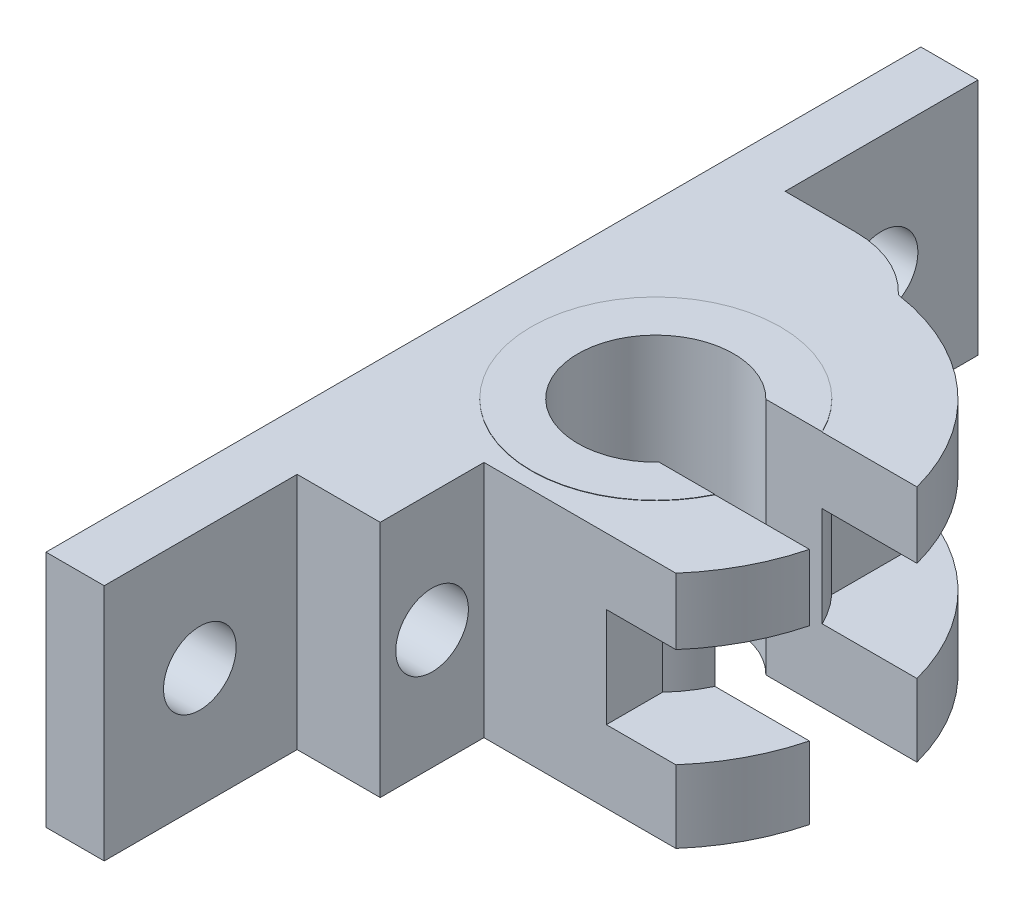
SolidWorks part; units mm, degrees
ref_plane "前基準面" through (0, 0, 0) normal (0, 0, 1) x (1, 0, 0)
ref_plane "上基準面" through (0, 0, 0) normal (0, 1, 0) x (1, 0, 0)
ref_plane "右基準面" through (0, 0, 0) normal (1, 0, 0) x (0, 0, -1)
sketch "草圖1" plane through (0, 0, 0) normal (0, 1, 0) x (1, 0, 0)
  circle A0 centre (0, 0) radius 9.68
  dimension "D1" = 19.36
extrude "伸長-薄件1" add sketch "草圖1" along normal blind 116.68 thin thin type one direction wall 11
ref_plane "平面1" through (-21, 0, 0) normal (1, 0, 0) x (0, 0, -1)
sketch "草圖11" plane through (0, 116.68, 0) normal (0, 1, 0) x (1, 0, 0)
  line L0 (-993.1634, -44.2358) -> (49006.8366, -44.2358) construction
  line L2 (35.2085, 30.7642) -> (8.2085, 30.7642)
  line L3 (35.2085, 30.7642) -> (35.2085, -119.2358)
  line L4 (35.2085, -119.2358) -> (8.2085, -119.2358)
  line L5 (8.2085, 30.7642) -> (8.2085, -119.2358)
  line L6 (35.2085, 30.7642) -> (8.2085, -119.2358) construction
  line L7 (35.2085, -119.2358) -> (8.2085, 30.7642) construction
  circle A0 centre (0, 0) radius 20.68 construction
  point P1 (21.7085, -44.2358)
  dimension "D1" = 150
  dimension "D2" = 27
  dimension "D3" = 30.7642
extrude "除料-伸長3" cut sketch "草圖11" against normal blind 40
ref_plane "平面2" through (0, 0, 21) normal (0, 0, 1) x (1, 0, 0)
sketch "草圖13" plane through (0, 0, 21) normal (0, 0, 1) x (1, 0, 0)
  line L0 (-21, -22.649) -> (-21, 22.649) construction
  line L1 (-21, 122.7847) -> (-11, 122.7847)
  line L2 (-21, 122.7847) -> (-21, -5.5603)
  line L3 (-21, -5.5603) -> (-11, -5.5603)
  line L4 (-11, 122.7847) -> (-11, -5.5603)
  dimension "D1" = 10
extrude "除料-伸長7" cut sketch "草圖13" against normal through all
sketch "草圖15" plane through (0, 0, 21) normal (0, 0, 1) x (1, 0, 0)
  line L0 (-1.3957, -883.32) -> (-1.3957, 49116.68) construction
  line L1 (8.2085, 116.68) -> (-11, 116.68) construction
  line L2 (-11, 0) -> (20.68, 0) construction
  line L3 (2.6043, 86.68) -> (-5.3957, 86.68)
  line L4 (2.6043, 86.68) -> (2.6043, 18)
  line L5 (2.6043, 18) -> (-5.3957, 18)
  line L6 (-5.3957, 86.68) -> (-5.3957, 18)
  line L7 (2.6043, 86.68) -> (-5.3957, 18) construction
  line L8 (2.6043, 18) -> (-5.3957, 86.68) construction
  point P1 (-1.3957, 52.34)
  point P5 (-1.3957, 116.68)
  dimension "D1" = 30
  dimension "D2" = 18
  dimension "D3" = 8
extrude "除料-伸長9" cut sketch "草圖15" against normal blind 48
sketch "草圖16" plane through (8.2085, 0, 0) normal (1, 0, 0) x (0, 0, -1)
  line L0 (20.68, 86.68) -> (20.68, 116.68) construction
  line L1 (5.1306, 116.68) -> (20.68, 116.68)
  line L2 (5.1306, 116.68) -> (5.1306, 96.68)
  line L3 (5.1306, 96.68) -> (20.68, 96.68)
  line L4 (20.68, 116.68) -> (20.68, 96.68)
  line L5 (-5.1306, 76.68) -> (-5.1306, 116.68) construction
  line L6 (-5.1306, 96.68) -> (-20.59, 96.68)
  line L7 (-5.1306, 96.68) -> (-5.1306, 116.68)
  line L8 (-5.1306, 116.68) -> (-20.59, 116.68)
  line L9 (-20.59, 96.68) -> (-20.59, 116.68)
  line L10 (-17.5118, 116.68) -> (-20.68, 116.68) construction
  dimension "D1" = 20
extrude "填料-伸長4" add sketch "草圖16" against normal blind 19.2
sketch "草圖17" plane through (0, 116.68, 0) normal (0, 1, 0) x (1, 0, 0)
  line L0 (-1009.59, 0) -> (48990.41, 0) construction
  line L1 (8.2085, 20.68) -> (8.2085, 5.1306) construction
  line L2 (8.2085, 6.97) -> (-11, 6.97)
  line L3 (8.2085, 6.97) -> (8.2085, -7.06)
  line L4 (8.2085, -7.06) -> (-11, -7.06)
  line L5 (-11, 6.97) -> (-11, -7.06)
  line L6 (-11, -17.5118) -> (-11, 17.5118) construction
  line L7 (-10.9915, -20.59) -> (-1.9273, -20.59) construction
  arc A0 (-8.2085, 5.1306) -> (-8.2085, -5.1306) centre (0, 0) ccw construction
  point P6 (-9.68, 0)
  dimension "D1" = 14.03
  dimension "D2" = 13.53
extrude "除料-伸長10" cut sketch "草圖17" against normal blind 20.2
sketch "草圖18" plane through (0, 0, 0) normal (0, -1, 0) x (1, 0, 0)
  circle A0 centre (0, 0) radius 9.59
extrude "除料-伸長11" cut sketch "草圖18" against normal through all
sketch "草圖21" plane through (0, 0, -20.68) normal (0, 0, -1) x (-1, 0, 0)
  line L0 (1.3915, 96.68) -> (1.3915, 105.73) construction
  line L1 (0, 96.68) -> (10.9915, 96.68) construction
  line L2 (1.3915, 105.73) -> (1.3915, 108.73) construction
  circle A0 centre (1.3915, 108.73) radius 2.985
  dimension "D3" = 5.97
  dimension "D1" = 9.05
  dimension "D2" = 3
extrude "除料-伸長12" cut sketch "草圖21" against normal blind 55.2
sketch "草圖23" plane through (0, 0, -20.68) normal (0, 0, -1) x (-1, 0, 0)
  line L0 (1.3915, 105.745) -> (1.3915, -11.785) construction
  circle A0 centre (1.3915, 108.73) radius 2.985 construction
  dimension "D1" = 117.53
sketch "草圖24" plane through (0, 0, 0) normal (0, -1, 0) x (1, 0, 0)
  circle A0 centre (0, 0) radius 9.59
extrude "伸長-薄件2" add sketch "草圖24" along normal blind 55.2 thin thin type one direction wall 11
sketch "草圖25" plane through (0, 0, 21) normal (0, 0, 1) x (1, 0, 0)
  line L0 (-1.3915, -11.785) -> (22.6124, -11.785)
  line L1 (22.6124, -11.785) -> (22.6124, -63.8733)
  line L2 (-22.7495, -63.8733) -> (22.6124, -63.8733)
  line L3 (-22.7495, -63.8733) -> (-22.7495, -11.785)
  line L4 (-22.7495, -11.785) -> (-1.3915, -11.785)
extrude "除料-伸長13" cut sketch "草圖25" against normal blind 55.2
sketch "草圖26" plane through (0, 0, 0) normal (0, 1, 0) x (1, 0, 0)
  line L0 (-21, -22.649) -> (-21, 22.649) construction
  line L1 (-10.9915, 20.68) -> (-21, 20.68)
  line L2 (-10.9915, 20.68) -> (-10.9915, -21)
  line L3 (-10.9915, -21) -> (-21, -21)
  line L4 (-21, 20.68) -> (-21, -21)
  line L5 (-17.6, -21) -> (17.6, -21) construction
extrude "除料-伸長15" cut sketch "草圖26" against normal blind 55.2
ref_plane "平面3" through (21, 0, 0) normal (1, 0, 0) x (0, 0, -1)
sketch "草圖27" plane through (21, 0, 0) normal (1, 0, 0) x (0, 0, -1)
  line L0 (0, -923.32) -> (0, 49076.68) construction
  line L1 (5.1306, 76.68) -> (-5.1306, 76.68) construction
  line L2 (18.9811, 76.68) -> (-18.9811, 76.68) construction
  line L3 (-5, 61.68) -> (5, 61.68)
  line L4 (-5, 61.68) -> (-5, 21.68)
  line L5 (-5, 21.68) -> (5, 21.68)
  line L6 (5, 61.68) -> (5, 21.68)
  line L7 (-5, 61.68) -> (5, 21.68) construction
  line L8 (-5, 21.68) -> (5, 61.68) construction
  point P1 (0, 41.68)
  point P5 (0, 76.68)
  dimension "D1" = 15
  dimension "D2" = 40
  dimension "D3" = 10
extrude "除料-伸長16" cut sketch "草圖27" against normal blind 55.2
sketch "草圖28" plane through (21, 0, 0) normal (1, 0, 0) x (0, 0, -1)
  line L1 (-22.4403, 4.804) -> (22.4403, 4.804)
  line L2 (-22.4403, 4.804) -> (-22.4403, -4.804)
  line L3 (-22.4403, -4.804) -> (22.4403, -4.804)
  line L4 (22.4403, 4.804) -> (22.4403, -4.804)
  line L5 (-22.4403, 4.804) -> (22.4403, -4.804) construction
  line L6 (-22.4403, -4.804) -> (22.4403, 4.804) construction
  point P0 (0, 0)
extrude "除料-伸長17" cut sketch "草圖28" against normal blind 12.2
sketch "草圖35" plane through (-10.9915, 0, 0) normal (-1, 0, 0) x (0, 0, 1)
  line L0 (20.59, 116.68) -> (20.59, 96.68)
  line L1 (20.59, 96.68) -> (7.06, 96.68)
  line L2 (7.06, 96.68) -> (7.06, 116.68)
  line L3 (7.06, 116.68) -> (20.59, 116.68)
extrude "填料-伸長10" add sketch "草圖35" along normal blind 15
sketch "草圖36" plane through (-10.9915, 0, 0) normal (-1, 0, 0) x (0, 0, 1)
  line L0 (-20.68, 116.68) -> (-6.97, 116.68)
  line L1 (-6.97, 116.68) -> (-6.97, 96.48)
  line L2 (-6.97, 96.48) -> (-20.68, 96.68)
  line L3 (-20.68, 96.68) -> (-20.68, 116.68)
extrude "填料-伸長11" add sketch "草圖36" along normal blind 15
sketch "草圖37" plane through (0, 0, 20.59) normal (0, 0, 1) x (1, 0, 0)
  line L0 (-25.9915, 96.68) -> (-1.9273, 96.68) construction
  line L1 (-25.9915, 116.68) -> (-16.9915, 116.68)
  line L2 (-25.9915, 116.68) -> (-25.9915, 96.68)
  line L3 (-25.9915, 96.68) -> (-16.9915, 96.68)
  line L4 (-16.9915, 116.68) -> (-16.9915, 96.68)
  dimension "D1" = 9
extrude "填料-伸長12" add sketch "草圖37" along normal blind 20
sketch "草圖38" plane through (0, 0, -20.68) normal (0, 0, -1) x (-1, 0, 0)
  line L0 (25.9915, 116.68) -> (-8.2085, 116.68) construction
  line L1 (25.9915, 96.68) -> (16.9915, 96.68)
  line L2 (25.9915, 96.68) -> (25.9915, 116.68)
  line L3 (25.9915, 116.68) -> (16.9915, 116.68)
  line L4 (16.9915, 96.68) -> (16.9915, 116.68)
  dimension "D1" = 9
extrude "填料-伸長13" add sketch "草圖38" along normal blind 20
sketch "草圖42" plane through (-16.9915, 0, 0) normal (1, 0, 0) x (0, 0, -1)
  line L0 (30.68, -903.32) -> (30.68, 49096.68) construction
  line L1 (40.68, 96.68) -> (20.68, 96.68) construction
  line L2 (-959.32, 106.68) -> (49040.68, 106.68) construction
  line L3 (40.68, 116.68) -> (40.68, 96.68) construction
  line L4 (-30.59, -903.32) -> (-30.59, 49096.68) construction
  line L5 (-40.59, 96.68) -> (-20.59, 96.68) construction
  circle A0 centre (30.68, 106.5544) radius 2.985
  circle A1 centre (-30.3956, 106.68) radius 2.985
  point P5 (30.68, 96.68)
  point P10 (40.68, 106.68)
  point P15 (-30.59, 96.68)
  dimension "D1" = 5.97
  dimension "D2" = 5.97
extrude "除料-伸長21" cut sketch "草圖42" against normal blind 20
sketch "草圖43" plane through (0, 116.68, 0) normal (0, 1, 0) x (1, 0, 0)
  line L0 (-11, 6.97) -> (-10.9915, 20.68)
  line L1 (-10.9915, 20.68) -> (-10.9915, 48.0968)
  line L2 (-10.9915, 48.0968) -> (-28.2748, 48.0968)
  line L3 (-28.2748, 48.0968) -> (-28.2748, -43.2705)
  line L4 (-28.2748, -43.2705) -> (-11, -43.2705)
  line L5 (-11, -43.2705) -> (-11, 6.97)
extrude "除料-伸長23" cut sketch "草圖43" against normal through all
sketch "草圖45" plane through (0, 0, 20.59) normal (0, 0, 1) x (1, 0, 0)
  line L0 (-11, 96.68) -> (-1.9273, 96.68) construction
  line L1 (-11, 116.68) -> (-8, 116.68)
  line L2 (-11, 116.68) -> (-11, 96.68)
  line L3 (-11, 96.68) -> (-8, 96.68)
  line L4 (-8, 116.68) -> (-8, 96.68)
  dimension "D1" = 3
extrude "填料-伸長14" add sketch "草圖45" along normal blind 30
sketch "草圖46" plane through (0, 0, -20.68) normal (0, 0, -1) x (-1, 0, 0)
  line L0 (0, 96.68) -> (10.9915, 96.68) construction
  line L1 (10.9915, 116.68) -> (7.9915, 116.68)
  line L2 (10.9915, 116.68) -> (10.9915, 96.68)
  line L3 (10.9915, 96.68) -> (7.9915, 96.68)
  line L4 (7.9915, 116.68) -> (7.9915, 96.68)
  dimension "D1" = 3
extrude "填料-伸長15" add sketch "草圖46" along normal blind 30
sketch "草圖47" plane through (-11, 0, 0) normal (-1, 0, 0) x (0, 0, 1)
  line L0 (50.59, 116.68) -> (7.06, 116.68) construction
  line L1 (50.59, 96.68) -> (17.5118, 96.68)
  line L2 (50.59, 96.68) -> (50.59, 116.68)
  line L3 (50.59, 116.68) -> (17.5118, 116.68)
  line L4 (17.5118, 96.68) -> (17.5118, 116.68)
extrude "填料-伸長16" add sketch "草圖47" along normal blind 50
sketch "草圖48" plane through (-10.9915, 0, 0) normal (-1, 0, 0) x (0, 0, 1)
  line L1 (-50.68, 116.68) -> (-20.68, 116.68)
  line L2 (-50.68, 116.68) -> (-50.68, 96.68)
  line L3 (-50.68, 96.68) -> (-20.68, 96.68)
  line L4 (-20.68, 116.68) -> (-20.68, 96.68)
extrude "填料-伸長17" add sketch "草圖48" along normal blind 50
sketch "草圖50" plane through (0, 0, 17.5118) normal (0, 0, -1) x (-1, 0, 0)
  line L0 (11, 96.68) -> (11, 116.68)
  line L1 (11, 116.68) -> (61, 116.68)
  line L2 (61, 116.68) -> (61, 96.68)
  line L3 (61, 96.68) -> (11, 96.68)
extrude "填料-伸長18" add sketch "草圖50" along normal blind 1
sketch "草圖51" plane through (0, 0, -20.68) normal (0, 0, 1) x (1, 0, 0)
  line L0 (-10.9915, 116.68) -> (-10.9915, 96.68)
  line L1 (-10.9915, 96.68) -> (-60.9915, 96.68)
  line L2 (-60.9915, 96.68) -> (-60.9915, 116.68)
  line L3 (-60.9915, 116.68) -> (-10.9915, 116.68)
extrude "填料-伸長19" add sketch "草圖51" along normal blind 1
sketch "草圖52" plane through (0, 116.68, 0) normal (0, 1, 0) x (1, 0, 0)
  line L0 (-34.4915, -949.32) -> (-34.4915, 49050.68) construction
  line L1 (-60.9915, 50.68) -> (-7.9915, 50.68) construction
  line L2 (-1007.9915, 35.68) -> (48992.0085, 35.68) construction
  line L3 (-7.9915, 50.68) -> (-7.9915, 20.68) construction
  line L4 (-60.9915, 19.68) -> (-60.9915, 50.68) construction
  line L5 (-7.9915, 50.68) -> (-60.9915, 50.68)
  line L6 (-7.9915, 50.68) -> (-7.9915, 36.68)
  line L7 (-7.9915, 36.68) -> (-60.9915, 36.68)
  line L8 (-60.9915, 50.68) -> (-60.9915, 36.68)
  point P5 (-34.4915, 50.68)
  point P10 (-7.9915, 35.68)
  dimension "D1" = 14
extrude "除料-伸長24" cut sketch "草圖52" against normal through all
sketch "草圖53" plane through (0, 116.68, 0) normal (0, 1, 0) x (1, 0, 0)
  line L0 (-61, -50.59) -> (-61, -16.5118) construction
  line L1 (-8, -50.59) -> (-61, -50.59)
  line L2 (-8, -50.59) -> (-8, -36.59)
  line L3 (-8, -36.59) -> (-61, -36.59)
  line L4 (-61, -50.59) -> (-61, -36.59)
  dimension "D1" = 14
extrude "除料-伸長25" cut sketch "草圖53" against normal through all
sketch "草圖54" plane through (0, 116.68, 0) normal (0, 1, 0) x (1, 0, 0)
  line L0 (-60.9915, 36.68) -> (-7.9915, 36.68) construction
  line L1 (-61, -36.59) -> (-21, -36.59)
  line L2 (-61, -36.59) -> (-61, 36.68)
  line L3 (-61, 36.68) -> (-21, 36.68)
  line L4 (-21, -36.59) -> (-21, 36.68)
  dimension "D1" = 40
extrude "除料-伸長26" cut sketch "草圖54" against normal through all
sketch "草圖55" plane through (0, 116.68, 0) normal (0, 1, 0) x (1, 0, 0)
  line L0 (-15.0276, -36.59) -> (-15.0276, -16.5118) construction
  line L1 (-8, -36.59) -> (-21, -36.59) construction
  line L2 (-21, -16.5118) -> (-11, -16.5118) construction
  line L3 (-13.4574, 19.68) -> (-13.4574, 39.76) construction
  line L4 (-10.9921, 19.68) -> (-21, 19.68) construction
  dimension "D1" = 20.08
sketch "草圖56" plane through (0, 0, -36.68) normal (0, 0, -1) x (-1, 0, 0)
  line L1 (7.9915, 96.68) -> (21, 96.68)
  line L2 (7.9915, 96.68) -> (7.9915, 116.68)
  line L3 (7.9915, 116.68) -> (21, 116.68)
  line L4 (21, 96.68) -> (21, 116.68)
extrude "填料-伸長21" add sketch "草圖56" along normal blind 3.08
ref_plane "平面4" through (0, 0, 50) normal (0, 0, 1) x (1, 0, 0)
sketch "草圖60" plane through (0, 116.68, 0) normal (0, 1, 0) x (1, 0, 0)
  line L0 (-21, 39.76) -> (-7.9915, 39.76) construction
  line L1 (-21, -36.59) -> (-14.4957, -36.59)
  line L2 (-21, -36.59) -> (-21, 39.76)
  line L3 (-21, 39.76) -> (-14.4957, 39.76)
  line L4 (-14.4957, -36.59) -> (-14.4957, 39.76)
extrude "除料-伸長30" cut sketch "草圖60" against normal through all
sketch "草圖61" plane through (0, 116.68, 0) normal (0, 1, 0) x (1, 0, 0)
  line L0 (1.9273, -20.59) -> (1.9273, -22.3991)
  line L1 (1.9273, -22.3991) -> (-2.1742, -21.4215)
  line L2 (-2.1742, -21.4215) -> (-2.1742, -20.59)
  line L3 (-8, -20.59) -> (-1.9273, -20.59) construction
  line L4 (-2.1742, -20.59) -> (1.9273, -20.59)
extrude "除料-伸長32" cut sketch "草圖61" against normal blind 20
sketch "草圖64" plane through (0, 116.68, 0) normal (0, 1, 0) x (1, 0, 0)
  line L1 (-8, -20.59) -> (8.2085, -20.59)
  line L2 (-8, -20.59) -> (-8, -20.68)
  line L3 (-8, -20.68) -> (8.2085, -20.68)
  line L4 (8.2085, -20.59) -> (8.2085, -20.68)
  dimension "D1" = 0.09
extrude "填料-伸長22" add sketch "草圖64" against normal blind 20
sketch "草圖65" plane through (0, 116.68, 0) normal (0, 1, 0) x (1, 0, 0)
  line L0 (-11, 6.97) -> (-10.9921, 19.68) construction
  line L1 (-11, -7.06) -> (-11, -16.5118) construction
  line L2 (-14.4957, -36.59) -> (-14.4957, -16.5118) construction
  line L3 (-11, -16.5118) -> (-14.4957, -16.5118)
  line L4 (-11, -16.5118) -> (-11, -19.7718)
  line L5 (-11, -19.7718) -> (-14.4957, -19.7718)
  line L6 (-14.4957, -16.5118) -> (-14.4957, -19.7718)
  dimension "D1" = 12.71
  dimension "D2" = 9.4518
  dimension "D3" = 3.26
extrude "除料-伸長33" cut sketch "草圖65" against normal through all
sketch "草圖66" plane through (0, 96.48, 0) normal (0, 1, 0) x (1, 0, 0)
  line L0 (-1011, -0.045) -> (48989, -0.045) construction
  line L1 (-11, 6.97) -> (-11, -7.06) construction
  line L2 (-12.9194, -0.045) -> (-12.9194, 17.905) construction
  line L3 (-12.9194, -0.045) -> (-12.9194, -17.995) construction
  line L4 (-11, -19.7718) -> (-11, -7.06) construction
  line L5 (-14.4957, -19.7718) -> (-11, -19.7718)
  line L6 (-14.4957, -19.7718) -> (-14.4957, -17.995)
  line L7 (-14.4957, -17.995) -> (-11, -17.995)
  line L8 (-11, -19.7718) -> (-11, -17.995)
  line L10 (-10.9921, 19.68) -> (-14.4957, 19.68)
  line L11 (-10.9921, 19.68) -> (-10.9921, 17.905)
  line L12 (-10.9921, 17.905) -> (-14.4957, 17.905)
  line L13 (-14.4957, 19.68) -> (-14.4957, 17.905)
  point P5 (-11, -0.045)
  dimension "D1" = 17.95
  dimension "D2" = 17.95
extrude "填料-伸長23" add sketch "草圖66" along normal blind 20.2
sketch "草圖68" plane through (0, 116.68, 0) normal (0, 1, 0) x (1, 0, 0)
  line L0 (-10.9932, 17.905) -> (-10.9932, 39.76) construction
  line L1 (-14.4957, 39.76) -> (-7.9915, 39.76) construction
  line L2 (-14.4957, 17.905) -> (-14.4957, 39.76) construction
  line L3 (-7.9915, 39.76) -> (-14.4957, 39.76)
  line L4 (-7.9915, 39.76) -> (-7.9915, 36.1)
  line L5 (-7.9915, 36.1) -> (-14.4957, 36.1)
  line L6 (-14.4957, 39.76) -> (-14.4957, 36.1)
  dimension "D1" = 3.66
extrude "除料-伸長34" cut sketch "草圖68" against normal blind 20
sketch "草圖69" plane through (-7.9915, 0, 0) normal (1, 0, 0) x (0, 0, -1)
  line L0 (28.39, -903.32) -> (28.39, 49096.68) construction
  line L1 (36.1, 96.68) -> (20.68, 96.68) construction
  line L2 (-28.635, -903.32) -> (-28.635, 49096.68) construction
  line L3 (-36.59, 96.68) -> (-20.68, 96.68) construction
  line L4 (-963.9, 106.68) -> (49036.1, 106.68) construction
  line L5 (36.1, 96.68) -> (36.1, 116.68) construction
  circle A0 centre (28.39, 106.68) radius 2.985
  circle A1 centre (-28.635, 106.68) radius 2.985
  point P5 (28.39, 96.68)
  point P10 (-28.635, 96.68)
  point P15 (36.1, 106.68)
  dimension "D1" = 5.97
  dimension "D2" = 5.97
extrude "除料-伸長35" cut sketch "草圖69" against normal through all
sketch "草圖70" plane through (0, 0, 20.59) normal (0, 0, -1) x (-1, 0, 0)
  circle A0 centre (1.3915, 108.73) radius 2.985
  dimension "D1" = 5.97
extrude "除料-伸長36" cut sketch "草圖70" against normal through all
sketch "草圖71" plane through (0, 0, 50) normal (0, 0, 1) x (1, 0, 0)
  line L1 (-16.2413, 123.1465) -> (21.764, 123.1465)
  line L2 (-16.2413, 123.1465) -> (-16.2413, 11.1806)
  line L3 (-16.2413, 11.1806) -> (21.764, 11.1806)
  line L4 (21.764, 123.1465) -> (21.764, 11.1806)
extrude "除料-伸長37" cut sketch "草圖71" against normal through all
sketch "草圖72" plane through (0, -11.785, 0) normal (0, -1, 0) x (1, 0, 0)
  circle A0 centre (0, 0) radius 9.7
  dimension "D1" = 19.4
extrude "除料-伸長38" cut sketch "草圖72" against normal through all
sketch "草圖77" plane through (0, 11.1806, 0) normal (0, 1, 0) x (1, 0, 0)
  circle A0 centre (0, 0) radius 20.59
  dimension "D1" = 41.18
extrude "除料-伸長-薄件2" cut sketch "草圖77" against normal blind 22 thin thin type one direction wall 10
sketch "草圖78" plane through (-11, 0, 0) normal (-1, 0, 0) x (0, 0, 1)
  line L1 (17.4054, 11.1806) -> (-17.4108, 11.1806)
  line L2 (17.4054, 11.1806) -> (17.4054, -11.785)
  line L3 (17.4054, -11.785) -> (-17.4108, -11.785)
  line L4 (-17.4108, 11.1806) -> (-17.4108, -11.785)
extrude "填料-伸長26" add sketch "草圖78" along normal blind 0.1
sketch "草圖80" plane through (0, -11.785, 0) normal (0, -1, 0) x (1, 0, 0)
  line L1 (-11.1, -17.4108) -> (-14, -17.4108)
  line L2 (-11.1, -17.4108) -> (-11.1, -23.5595)
  line L3 (-11.1, -23.5595) -> (-14, -23.5595)
  line L4 (-14, -17.4108) -> (-14, -23.5595)
extrude "填料-伸長28" add sketch "草圖80" against normal blind 23.1 separate body
sketch "草圖81" plane through (-11.1, 0, 0) normal (1, 0, 0) x (0, 0, -1)
  line L0 (17.4108, -11.785) -> (23.5595, -11.785)
  line L1 (23.5595, -11.785) -> (23.5595, 11.315)
  line L2 (23.5595, 11.315) -> (17.4108, 11.315)
  line L3 (17.4108, 11.315) -> (17.4108, -11.785)
extrude "填料-伸長29" add sketch "草圖81" along normal blind 14.1
sketch "草圖82" plane through (3, 0, 0) normal (1, 0, 0) x (0, 0, -1)
  line L0 (17.4108, 11.1806) -> (17.4108, 11.315)
  line L1 (17.4108, 11.315) -> (23.5595, 11.315)
  line L2 (23.5595, 11.315) -> (23.5595, 11.1806)
  line L3 (23.5595, -11.785) -> (23.5595, 11.315) construction
  line L4 (23.5595, 11.1806) -> (17.4108, 11.1806)
extrude "除料-伸長39" cut sketch "草圖82" against normal blind 19.1
sketch "草圖83" plane through (0, 0, -17.4108) normal (0, 0, 1) x (1, 0, 0)
  line L1 (-11.1, 11.1806) -> (-14, 11.1806)
  line L2 (-11.1, 11.1806) -> (-11.1, -11.785)
  line L3 (-11.1, -11.785) -> (-14, -11.785)
  line L4 (-14, 11.1806) -> (-14, -11.785)
extrude "填料-伸長30" add sketch "草圖83" against normal blind 19.1
fillet "圓角1" radius 10 1 edges at (3, -0.3022, -23.5595)
sketch "草圖84" plane through (0, -11.785, 0) normal (0, -1, 0) x (-1, 0, 0)
  line L1 (11.1, 17.4108) -> (14.6, 17.4108)
  line L2 (11.1, 17.4108) -> (11.1, 36.5108)
  line L3 (11.1, 36.5108) -> (14.6, 36.5108)
  line L4 (14.6, 17.4108) -> (14.6, 36.5108)
  dimension "D1" = 3.5
extrude "填料-伸長31" add sketch "草圖84" against normal blind 23.1
sketch "草圖85" plane through (0, -11.785, 0) normal (0, -1, 0) x (1, 0, 0)
  line L0 (-11.1, -17.4108) -> (-11.1, -35.9908) construction
  line L1 (-11.1, -36.5108) -> (-11.1, -23.5595) construction
  line L3 (-11.1, -35.9908) -> (-14.6, -35.9908)
  line L4 (-11.1, -35.9908) -> (-11.1, -36.5108)
  line L5 (-11.1, -36.5108) -> (-14.6, -36.5108)
  line L6 (-14.6, -35.9908) -> (-14.6, -36.5108)
  dimension "D1" = 18.58
extrude "除料-伸長40" cut sketch "草圖85" against normal through all
sketch "草圖86" plane through (0, 0, -17.4108) normal (0, 0, 1) x (1, 0, 0)
  line L1 (-11.1, 11.1806) -> (-14.6, 11.1806)
  line L2 (-11.1, 11.1806) -> (-11.1, -11.785)
  line L3 (-11.1, -11.785) -> (-14.6, -11.785)
  line L4 (-14.6, 11.1806) -> (-14.6, -11.785)
extrude "填料-伸長32" add sketch "草圖86" along normal blind 62.1
sketch "草圖87" plane through (0, -11.785, 0) normal (0, -1, 0) x (1, 0, 0)
  line L0 (-14.6, 44.6892) -> (-14.6, -35.9908) construction
  line L1 (-10.9915, -17.4108) -> (-14.6, -17.4108)
  line L2 (-10.9915, -17.4108) -> (-10.9915, 17.4054)
  line L3 (-10.9915, 17.4054) -> (-14.6, 17.4054)
  line L4 (-14.6, -17.4108) -> (-14.6, 17.4054)
extrude "除料-伸長41" cut sketch "草圖87" against normal blind 62.1
sketch "草圖89" plane through (0, -11.785, 0) normal (0, -1, 0) x (1, 0, 0)
  line L0 (-10.9915, 17.4108) -> (-10.9915, 23.5608) construction
  line L1 (-11.1, 44.6892) -> (-11.1, 17.4054) construction
  line L2 (-11.1, 23.5608) -> (-10.9915, 23.5608)
  line L3 (-11.1, 23.5608) -> (-11.1, 17.4108)
  line L4 (-11.1, 17.4108) -> (-10.9915, 17.4108)
  line L5 (-10.9915, 23.5608) -> (-10.9915, 17.4108)
  dimension "D1" = 6.15
extrude "填料-伸長33" add sketch "草圖89" against normal blind 23.1
sketch "草圖90" plane through (0, 0, 23.5608) normal (0, 0, 1) x (1, 0, 0)
  line L0 (-11, 11.1806) -> (-11.1, 11.1806)
  line L1 (-11.1, 11.1806) -> (-11.1, -11.785)
  line L2 (-11.1, -11.785) -> (-10.9915, -11.785)
  line L3 (-10.9915, -11.785) -> (-10.9915, 11.1806)
  line L4 (-10.9915, 11.1806) -> (-11, 11.1806)
extrude "填料-伸長34" add sketch "草圖90" along normal blind 22.1
sketch "草圖91" plane through (-11.1, 0, 0) normal (-1, 0, 0) x (0, 0, 1)
  line L1 (45.6608, -11.785) -> (44.6892, -11.785)
  line L2 (45.6608, -11.785) -> (45.6608, 11.1806)
  line L3 (45.6608, 11.1806) -> (44.6892, 11.1806)
  line L4 (44.6892, -11.785) -> (44.6892, 11.1806)
extrude "除料-伸長42" cut sketch "草圖91" against normal blind 22.1
sketch "草圖93" plane through (0, -11.785, 0) normal (0, -1, 0) x (1, 0, 0)
  line L0 (-10.9915, 17.4108) -> (-10.9915, 23.5608) construction
  line L1 (-10.9915, 17.4108) -> (-10.9915, 44.6892) construction
  dimension "D1" = 6.15
sketch "草圖94" plane through (-10.9915, 0, 0) normal (1, 0, 0) x (0, 0, -1)
  line L0 (-23.5608, -11.785) -> (-23.5608, 11.1806) construction
  line L1 (-17.4108, -11.785) -> (-23.5608, -11.785) construction
sketch "草圖95" plane through (-10.9915, 0, 0) normal (1, 0, 0) x (0, 0, -1)
  line L1 (-23.5608, 11.1806) -> (-17.4108, 11.1806)
  line L2 (-17.4108, 11.315) -> (-17.4108, -11.785) construction
  line L3 (-17.4108, 11.1806) -> (-17.4108, -11.785)
  line L4 (-17.4108, -11.785) -> (-23.5608, -11.785)
  line L5 (-23.5608, -11.785) -> (-23.5608, 11.1806)
extrude "填料-伸長35" add sketch "草圖95" along normal blind 14.1
fillet "圓角2" radius 10 1 edges at (3.1085, -0.3022, 23.5608)
sketch "草圖96" plane through (0, -11.785, 0) normal (0, -1, 0) x (1, 0, 0)
  line L0 (-10.9915, 23.5608) -> (-10.9915, 42.1408) construction
  line L1 (-10.9915, 23.5608) -> (-10.9915, 44.6892) construction
  line L3 (-10.9915, 42.1408) -> (-14.6, 42.1408)
  line L4 (-10.9915, 42.1408) -> (-10.9915, 44.6892)
  line L5 (-10.9915, 44.6892) -> (-14.6, 44.6892)
  line L6 (-14.6, 42.1408) -> (-14.6, 44.6892)
  dimension "D1" = 18.58
extrude "除料-伸長43" cut sketch "草圖96" against normal through all
sketch "草圖97" plane through (0, -11.785, 0) normal (0, -1, 0) x (1, 0, 0)
  line L0 (-11.1, -23.5595) -> (-11.1, -42.1395) construction
  line L2 (-14.6, -35.9908) -> (-11.1, -35.9908)
  line L3 (-14.6, -35.9908) -> (-14.6, -42.1395)
  line L4 (-14.6, -42.1395) -> (-11.1, -42.1395)
  line L5 (-11.1, -35.9908) -> (-11.1, -42.1395)
  dimension "D1" = 18.58
extrude "填料-伸長36" add sketch "草圖97" against normal blind 23.1
sketch "草圖98" plane through (-11.1, 0, 0) normal (1, 0, 0) x (0, 0, -1)
  line L0 (17.4108, 11.1806) -> (17.4108, 11.315)
  line L1 (17.4108, 11.315) -> (22.1983, 11.315)
  line L2 (42.1395, 11.315) -> (17.4108, 11.315) construction
  line L3 (22.1983, 11.315) -> (38.4617, 11.315)
  line L4 (38.4617, 11.315) -> (42.1395, 11.315)
  line L5 (42.1395, 11.315) -> (42.1395, 11.1806)
  line L6 (42.1395, 11.315) -> (42.1395, -11.785) construction
  line L7 (42.1395, 11.1806) -> (17.4108, 11.1806)
extrude "除料-伸長44" cut sketch "草圖98" against normal blind 23.1
sketch "草圖99" plane through (-10.9915, 0, 0) normal (1, 0, 0) x (0, 0, -1)
  line L1 (-23.5608, 11.1806) -> (-17.4108, 11.1806)
  line L2 (-23.5608, 11.1806) -> (-23.5608, 11.315)
  line L3 (-23.5608, 11.315) -> (-17.4108, 11.315)
  line L4 (-17.4108, 11.1806) -> (-17.4108, 11.315)
extrude "除料-伸長45" cut sketch "草圖99" against normal blind 23.1
sketch "草圖100" plane through (-10.9915, 0, 0) normal (1, 0, 0) x (0, 0, -1)
  line L0 (-1042.1408, -0.3022) -> (48957.8592, -0.3022) construction
  line L1 (-42.1408, 11.1806) -> (-42.1408, -11.785) construction
  line L2 (-32.8508, -988.8194) -> (-32.8508, 49011.1806) construction
  line L3 (-42.1408, 11.1806) -> (-23.5608, 11.1806) construction
  line L4 (32.8495, -988.8194) -> (32.8495, 49011.1806) construction
  line L5 (23.5595, 11.1806) -> (42.1395, 11.1806) construction
  point P5 (-42.1408, -0.3022)
  point P10 (-32.8508, 11.1806)
  point P15 (32.8495, 11.1806)
sketch "草圖101" plane through (-10.9915, 0, 0) normal (1, 0, 0) x (0, 0, -1)
  line L0 (-201042.1408, -0.3022) -> (248957.8592, -0.3022) construction
  line L1 (32.8495, -200988.8194) -> (32.8495, 249011.1806) construction
  circle A0 centre (-32.9287, -0.3022) radius 2.985
  circle A1 centre (32.8495, -0.3022) radius 2.985
  dimension "D1" = 5.97
  dimension "D2" = 5.97
extrude "除料-伸長46" cut sketch "草圖101" against normal blind 23.1
sketch "草圖102" plane through (0, 11.1806, 0) normal (0, 1, 0) x (1, 0, 0)
  line L0 (-14.6, 42.1395) -> (-14.6, 17.4108) construction
  line L1 (-10.9915, 17.4108) -> (-14.6, 17.4108)
  line L2 (-10.9915, 17.4108) -> (-10.9915, 17.9508)
  line L3 (-10.9915, 17.9508) -> (-14.6, 17.9508)
  line L4 (-14.6, 17.4108) -> (-14.6, 17.9508)
  line L5 (-14.6, -42.1408) -> (-14.6, -17.4054) construction
  line L6 (-10.9915, -17.4108) -> (-14.6, -17.4108)
  line L7 (-10.9915, -17.4108) -> (-10.9915, -17.9508)
  line L8 (-10.9915, -17.9508) -> (-14.6, -17.9508)
  line L9 (-14.6, -17.4108) -> (-14.6, -17.9508)
  dimension "D1" = 0.54
  dimension "D2" = 0.54
sketch "草圖103" plane through (0, 11.1806, 0) normal (0, 1, 0) x (1, 0, 0)
  line L0 (-14.6, -17.4108) -> (-14.6, -17.9508) construction
  line L1 (-10.9915, -17.4054) -> (-14.6, -17.4054)
  line L2 (-10.9915, -17.4054) -> (-10.9915, -17.9454)
  line L3 (-10.9915, -17.9454) -> (-14.6, -17.9454)
  line L4 (-14.6, -17.4054) -> (-14.6, -17.9454)
  dimension "D1" = 0.54
extrude "除料-伸長49" cut sketch "草圖103" against normal through all
sketch "草圖104" plane through (0, 11.1806, 0) normal (0, 1, 0) x (1, 0, 0)
  line L0 (-14.6, 42.1395) -> (-14.6, 17.4108) construction
  line L1 (-10.9915, 17.4108) -> (-14.6, 17.4108)
  line L2 (-10.9915, 17.4108) -> (-10.9915, 17.9508)
  line L3 (-10.9915, 17.9508) -> (-14.6, 17.9508)
  line L4 (-14.6, 17.4108) -> (-14.6, 17.9508)
  dimension "D1" = 0.54
extrude "除料-伸長50" cut sketch "草圖104" against normal through all
sketch "草圖123" plane through (-14.6, 0, 0) normal (-1, 0, 0) x (0, 0, 1)
  line L0 (-17.9508, 11.1806) -> (17.9454, 11.1806) construction
  line L1 (-42.1395, -11.785) -> (-17.9508, -11.785)
  line L2 (-42.1395, -11.785) -> (-42.1395, 11.1806)
  line L3 (-42.1395, 11.1806) -> (-17.9508, 11.1806)
  line L4 (-17.9508, -11.785) -> (-17.9508, 11.1806)
  line L5 (-42.1395, 11.1806) -> (-17.9508, 11.1806) construction
  line L6 (42.1408, 11.1806) -> (17.9454, 11.1806) construction
  line L7 (17.9454, -11.785) -> (42.1408, -11.785)
  line L8 (17.9454, -11.785) -> (17.9454, 11.1806)
  line L9 (17.9454, 11.1806) -> (42.1408, 11.1806)
  line L10 (42.1408, -11.785) -> (42.1408, 11.1806)
extrude "填料-伸長37" add sketch "草圖123" along normal blind 2
sketch "草圖124" plane through (-14.6, 0, 0) normal (1, 0, 0) x (0, 0, -1)
  circle A0 centre (32.8495, -0.3022) radius 3.05
  circle A1 centre (-32.9287, -0.3022) radius 3.05
  dimension "D1" = 6.1
  dimension "D2" = 6.1
extrude "除料-伸長60" cut sketch "草圖124" against normal through all
sketch "草圖126" plane through (0, 11.1806, 0) normal (0, 1, 0) x (1, 0, 0)
  line L1 (35.5347, 4.2499) -> (5.6452, 4.2499)
  line L2 (35.5347, 4.2499) -> (35.5347, -4.1401)
  line L3 (35.5347, -4.1401) -> (5.6452, -4.1401)
  line L4 (5.6452, 4.2499) -> (5.6452, -4.1401)
  line L5 (35.5347, 4.2499) -> (5.6452, -4.1401) construction
  line L6 (35.5347, -4.1401) -> (5.6452, 4.2499) construction
  arc A0 (3.1085, -20.354) -> (3, 20.3703) centre (0, 0) ccw construction
  point P0 (20.5899, 0.0549)
  dimension "D1" = 8.39
extrude "除料-伸長61" cut sketch "草圖126" against normal through all
sketch "草圖127" plane through (-10.9915, 0, 0) normal (1, 0, 0) x (0, 0, -1)
  line L1 (-23.5608, 11.1806) -> (-42.1408, 11.1806)
  line L2 (-23.5608, 11.1806) -> (-23.5608, -11.785)
  line L3 (-23.5608, -11.785) -> (-42.1408, -11.785)
  line L4 (-42.1408, 11.1806) -> (-42.1408, -11.785)
extrude "填料-伸長38" add sketch "草圖127" along normal blind 10
sketch "草圖128" plane through (-16.6, 0, 0) normal (-1, 0, 0) x (0, 0, 1)
  circle A0 centre (32.9287, -0.3022) radius 3.25
  dimension "D1" = 6.5
extrude "除料-伸長62" cut sketch "草圖128" against normal through all
sketch "草圖129" plane through (-16.6, 0, 0) normal (-1, 0, 0) x (0, 0, 1)
  line L0 (-32.8495, -997.3172) -> (-32.8495, 49002.6828) construction
  line L1 (-1035.8995, -0.3022) -> (48964.1005, -0.3022) construction
  circle A3 centre (-32.8495, -0.3022) radius 3.25
  dimension "D1" = 6.5
extrude "除料-伸長63" cut sketch "草圖129" against normal through all
sketch "草圖130" plane through (0, 11.1806, 0) normal (0, 1, 0) x (1, 0, 0)
  line L0 (-4.2299, -23.5608) -> (-4.2299, -13.5608)
  line L1 (-4.2299, -13.5608) -> (20.7286, -13.5608)
  line L2 (20.7286, -13.5608) -> (20.7286, -23.5608)
  line L3 (20.7286, -23.5608) -> (-4.2299, -23.5608)
extrude "除料-伸長64" cut sketch "草圖130" against normal through all
sketch "草圖136" plane through (0, 11.1806, 0) normal (0, 1, 0) x (1, 0, 0)
  line L0 (-10.9915, -17.9454) -> (-10.9915, -23.5554) construction
  line L2 (-10.9915, -23.5554) -> (-0.9915, -23.5554)
  line L3 (-10.9915, -23.5554) -> (-10.9915, -42.1408)
  line L4 (-10.9915, -42.1408) -> (-0.9915, -42.1408)
  line L5 (-0.9915, -23.5554) -> (-0.9915, -42.1408)
  dimension "D1" = 5.61
extrude "除料-伸長68" cut sketch "草圖136" against normal blind 24
sketch "草圖138" plane through (0, 0, -17.9508) normal (0, 0, 1) x (1, 0, 0)
  line L0 (-10.9915, -11.785) -> (-16.6, -11.785)
  line L1 (-16.6, -11.785) -> (-16.6, 11.1806)
  line L2 (-16.6, 11.1806) -> (-10.9915, 11.1806)
  line L3 (-10.9915, 11.1806) -> (-10.9915, -11.785)
extrude "填料-伸長40" add sketch "草圖138" along normal blind 38
sketch "草圖141" plane through (-4.2299, 0, 0) normal (1, 0, 0) x (0, 0, -1)
  line L1 (-13.5608, -11.785) -> (-23.5554, -11.785)
  line L2 (-13.5608, -11.785) -> (-13.5608, 11.1806)
  line L3 (-13.5608, 11.1806) -> (-23.5554, 11.1806)
  line L4 (-23.5554, -11.785) -> (-23.5554, 11.1806)
extrude "填料-伸長41" add sketch "草圖141" along normal blind 3.24
sketch "草圖144" plane through (0, 11.1806, 0) normal (0, 1, 0) x (1, 0, 0)
  line L0 (-0.9899, -23.5554) -> (-10.9915, -23.5554) construction
  line L1 (-0.9899, -13.5608) -> (-2.9899, -13.5608)
  line L2 (-0.9899, -13.5608) -> (-0.9899, -23.5554)
  line L3 (-0.9899, -23.5554) -> (-2.9899, -23.5554)
  line L4 (-2.9899, -13.5608) -> (-2.9899, -23.5554)
  dimension "D1" = 2
extrude "除料-伸長70" cut sketch "草圖144" against normal blind 32.24
sketch "草圖146" plane through (-10.9915, 0, 0) normal (1, 0, 0) x (0, 0, -1)
  line L0 (-32.9287, -1003.5522) -> (-32.9287, 48996.4478) construction
  line L1 (32.8495, -1003.5522) -> (32.8495, 48996.4478) construction
  line L2 (-1029.6787, -0.3022) -> (48970.3213, -0.3022) construction
  circle A3 centre (-32.9287, -0.3022) radius 3.5
  circle A4 centre (32.8495, -0.3022) radius 3.5
  dimension "D1" = 7
  dimension "D2" = 7
extrude "除料-伸長72" cut sketch "草圖146" against normal through all
sketch "草圖150" plane through (-2.9899, 0, 0) normal (1, 0, 0) x (0, 0, -1)
  line L0 (-18.5581, -1011.785) -> (-18.5581, 48988.215) construction
  line L1 (-13.5608, -11.785) -> (-23.5554, -11.785) construction
  line L2 (-1029.4287, -0.3022) -> (48970.5713, -0.3022) construction
  circle A1 centre (-18.5581, -0.3022) radius 3.5
  point P5 (-18.5581, -11.785)
  dimension "D1" = 7
extrude "除料-伸長74" cut sketch "草圖150" against normal through all
sketch "草圖152" plane through (0, 11.1806, 0) normal (0, 1, 0) x (1, 0, 0)
  line L0 (20.1466, 4.2499) -> (8.7194, 4.2499) construction
  line L1 (28.4163, 5.2499) -> (5.6853, 5.2499)
  line L2 (28.4163, 5.2499) -> (28.4163, -5.1401)
  line L3 (28.4163, -5.1401) -> (5.6853, -5.1401)
  line L4 (5.6853, 5.2499) -> (5.6853, -5.1401)
  line L5 (28.4163, 5.2499) -> (5.6853, -5.1401) construction
  line L6 (28.4163, -5.1401) -> (5.6853, 5.2499) construction
  line L7 (8.7721, -4.1401) -> (20.1695, -4.1401) construction
  point P0 (17.0508, 0.0549)
  dimension "D1" = 1
  dimension "D2" = 1
extrude "除料-伸長75" cut sketch "草圖152" against normal blind 40.05
sketch "草圖153" plane through (0, -11.785, 0) normal (0, -1, 0) x (1, 0, 0)
  circle A0 centre (0, 0) radius 6.995
  dimension "D1" = 13.99
extrude "伸長-薄件3" add sketch "草圖153" against normal blind 23 thin thin type one direction wall 5
sketch "草圖155" plane through (0, -11.785, 0) normal (0, -1, 0) x (1, 0, 0)
  line L0 (10.8379, 5.1401) -> (1.1869, 5.1401)
  line L1 (1.1869, 5.1401) -> (4.1945, -5.2499)
  line L2 (4.1945, -5.2499) -> (13.4723, -5.2499)
  line L3 (19.9095, -5.2499) -> (10.7851, -5.2499) construction
  line L4 (13.4723, -5.2499) -> (13.4723, 5.1401)
  line L5 (10.8379, 5.1401) -> (19.9381, 5.1401) construction
  line L6 (13.4723, 5.1401) -> (10.8379, 5.1401)
extrude "除料-伸長76" cut sketch "草圖155" against normal blind 27
sketch "草圖156" plane through (0, -11.785, 0) normal (0, -1, 0) x (1, 0, 0)
  circle A0 centre (0, 0) radius 7.5
  dimension "D1" = 15
extrude "除料-伸長77" cut sketch "草圖156" against normal blind 40
